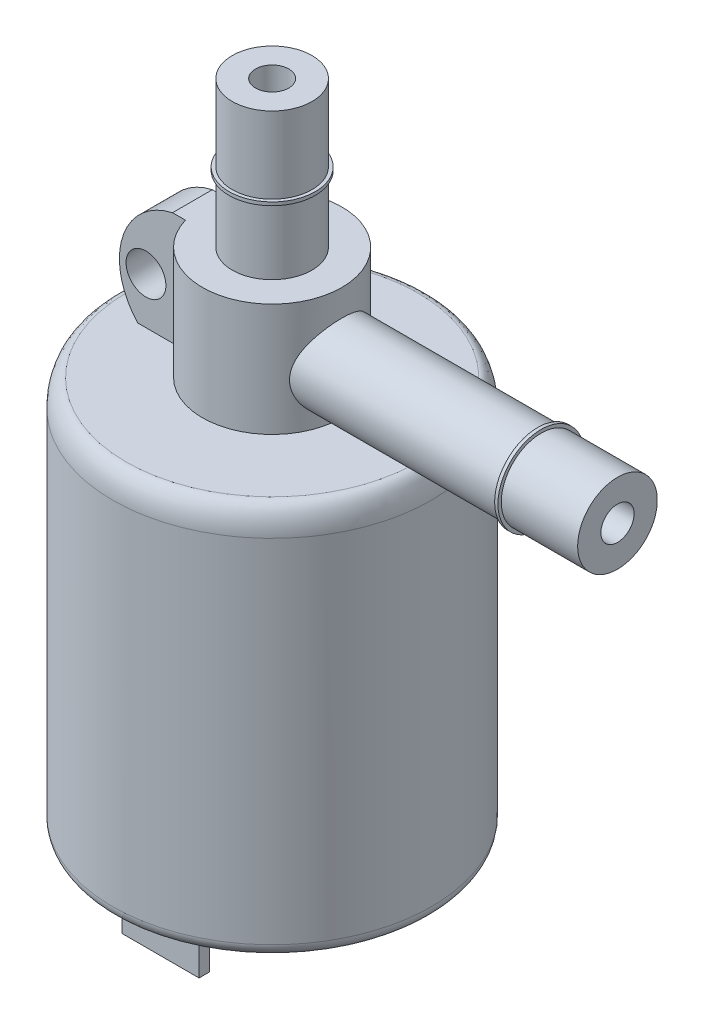
SolidWorks part; units mm, degrees
material "ABS"
ref_plane "Front" through (0, 0, 0) normal (0, 0, 1) x (1, 0, 0)
ref_plane "Top" through (0, 0, 0) normal (0, 1, 0) x (1, 0, 0)
ref_plane "Right" through (0, 0, 0) normal (1, 0, 0) x (0, 0, -1)
sketch "Esquisse1" plane through (0, 0, 0) normal (0, 0, 1) x (1, 0, 0)
  line L0 (0, 0) -> (12, 0)
  line L1 (12, 0) -> (12, 29.5)
  line L2 (12, 29.5) -> (5.25, 29.5)
  line L3 (5.25, 29.5) -> (5.25, 38)
  line L4 (5.25, 38) -> (3, 38)
  line L5 (3, 38) -> (3, 43)
  line L6 (3, 43) -> (3.25, 43)
  line L7 (3.25, 43) -> (3.25, 43.25)
  line L8 (3.25, 43.25) -> (3, 43.25)
  line L9 (3, 43.25) -> (3, 49)
  line L10 (3, 49) -> (1.25, 49)
  line L11 (1.25, 49) -> (1.25, 38)
  line L12 (1.25, 38) -> (0, 38)
  line L13 (0, 38) -> (0, 0)
  line L14 (0, 0) -> (0, -12) construction
  dimension "D1" = 38
  dimension "D2" = 29.5
  dimension "D3" = 24
  dimension "D4" = 10.5
  dimension "D5" = 2.5
  dimension "D6" = 6
  dimension "D7" = 6.5
  dimension "D8" = 11
  dimension "D9" = 5
revolve "Révolution1" add sketch "Esquisse1" angle 360 about L14
sketch "Esquisse2" plane through (0, 0, 0) normal (0, 0, 1) x (1, 0, 0)
  line L0 (0, 38) -> (-6, 38)
  line L1 (5.25, 38) -> (-5.25, 38) construction
  line L2 (-8, 33) -> (0, 33) construction
  line L3 (0, 28) -> (0, 38)
  line L4 (0, 28) -> (-6, 28)
  circle A0 centre (-8, 33) radius 1.5
  arc A1 (-6, 38) -> (-6, 28) centre (-4.875, 33) ccw
  dimension "D1" = 5
  dimension "D2" = 10
  dimension "D3" = 8
  dimension "D4" = 3
  dimension "D5" = 0.5
  dimension "D6" = 6
extrude "Boss.-Extru.1" add sketch "Esquisse2" along normal mid plane 3
sketch "Esquisse3" plane through (0, 0, 0) normal (0, 0, 1) x (1, 0, 0)
  line L0 (0, 36) -> (20, 36)
  line L1 (20, 36) -> (20, 36.25)
  line L2 (20, 36.25) -> (20.25, 36.25)
  line L3 (20.25, 36.25) -> (20.25, 36)
  line L4 (20.25, 36) -> (26, 36)
  line L5 (26, 36) -> (26, 34.25)
  line L6 (26, 34.25) -> (15, 34.25)
  line L7 (15, 34.25) -> (15, 33)
  line L8 (15, 33) -> (0, 33)
  line L9 (0, 33) -> (0, 36)
  line L10 (3, 43.25) -> (3, 49) construction
  line L11 (3, 49) -> (1.25, 49) construction
  line L12 (3.25, 43) -> (3.25, 43.25) construction
  line L13 (1.25, 38) -> (0, 38) construction
  line L14 (15, 33) -> (26, 33) construction
  line L15 (-12, 0) -> (12, 0) construction
  line L16 (-12, 29.5) -> (-12, 0) construction
  line L17 (1.25, 49) -> (1.25, 38) construction
  dimension "D1" = 33
  dimension "D2" = 38
revolve "Révolution3" add sketch "Esquisse3" angle 360 about L14
sketch "Esquisse4" plane through (0, 0, 0) normal (0, -1, 0) x (1, 0, 0)
  line L0 (50, 0) -> (-50, 0) construction
  line L1 (-4.25, 9.25) -> (4.25, 9.25)
  line L2 (-4.25, 9.25) -> (-4.25, 6.75)
  line L3 (-4.25, 6.75) -> (4.25, 6.75)
  line L4 (4.25, 9.25) -> (4.25, 6.75)
  line L9 (4.25, -9.25) -> (4.25, -6.75)
  line L10 (-4.25, -6.75) -> (4.25, -6.75)
  line L11 (-4.25, -9.25) -> (-4.25, -6.75)
  line L12 (-4.25, -9.25) -> (4.25, -9.25)
  line L13 (0, -50) -> (0, 50) construction
  circle A0 centre (0, 0) radius 5
  point P13 (0, 9.25)
  dimension "D1" = 2.5
  dimension "D4" = 10
  dimension "D2" = 18.5
  dimension "D3" = 8.5
extrude "Boss.-Extru.2" add sketch "Esquisse4" along normal blind 0.5
sketch "Esquisse5" plane through (0, 0, 0) normal (0, -1, 0) x (1, 0, 0)
  line L0 (50, 0) -> (-50, 0) construction
  line L1 (-2.9, 7.6) -> (2.9, 7.6)
  line L2 (-2.9, 7.6) -> (-2.9, 8.4)
  line L3 (-2.9, 8.4) -> (2.9, 8.4)
  line L4 (2.9, 7.6) -> (2.9, 8.4)
  line L5 (2.9, -7.6) -> (2.9, -8.4)
  line L6 (-2.9, -8.4) -> (2.9, -8.4)
  line L7 (-2.9, -7.6) -> (-2.9, -8.4)
  line L8 (-2.9, -7.6) -> (2.9, -7.6)
  line L9 (0, 9.25) -> (0, 7.6) construction
  line L10 (4.25, 9.25) -> (-4.25, 9.25) construction
  line L12 (-2.9, 8) -> (-4.25, 8) construction
  line L13 (-4.25, 9.25) -> (-4.25, 6.75) construction
  dimension "D1" = 0.8
  dimension "D2" = 5.8
extrude "Boss.-Extru.3" add sketch "Esquisse5" along normal blind 4
fillet "Congé2" radius 2 1 edges at (-12, 29.5, 0) second distance 1 first distance on face at (-12, 29.5, 0)
fillet "Congé3" radius 1 1 edges at (-12, 0, 0)
